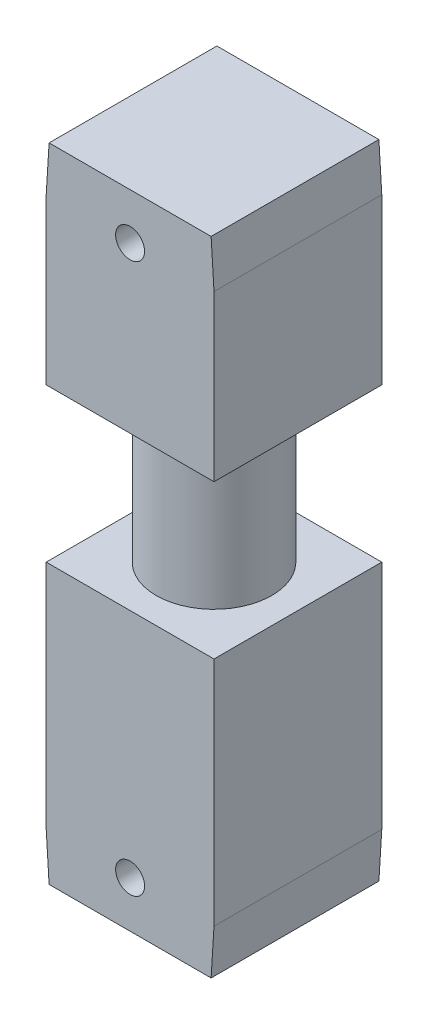
SolidWorks part; units mm, degrees
ref_plane "Front Plane" through (0, 0, 0) normal (0, 0, 1) x (1, 0, 0)
ref_plane "Top Plane" through (0, 0, 0) normal (0, 1, 0) x (1, 0, 0)
ref_plane "Right Plane" through (0, 0, 0) normal (1, 0, 0) x (0, 0, -1)
sketch "Sketch1" plane through (0, 0, 0) normal (0, 0, 1) x (1, 0, 0)
  line L0 (0, 0) -> (0, 106.5273) construction
  line L12 (-14.5, 40) -> (14.5, 40)
  line L13 (-14.5, 66.5273) -> (14.5, 66.5273)
  line L14 (-30, 0) -> (30, 0) construction
  line L16 (-30, 95) -> (30, 95) construction
  line L17 (-30, 103) -> (14, 103) construction
  line L18 (-30, -8) -> (14, -8) construction
  line L19 (-30, 53.2637) -> (30, 53.2637) construction
  line L20 (-14.5, 40) -> (-14.5, 0)
  line L21 (14.5, 40) -> (14.5, 0)
  line L22 (-14, 103) -> (14, 103)
  line L23 (-14.5, 66.5273) -> (-14.5, 95)
  line L24 (-14.5, 95) -> (-14, 103)
  line L25 (14.5, 66.5273) -> (14.5, 95)
  line L26 (14.5, 95) -> (14, 103)
  line L27 (-14, -8) -> (14, -8)
  line L28 (-14.5, 0) -> (-14, -8)
  line L29 (14, -8) -> (14.5, 0)
  circle A12 centre (0, 95) radius 2.5
  circle A13 centre (0, 0) radius 2.5
  point P20 (0, 53.2637)
  point P21 (-8, 103)
  point P34 (-8, -8)
  point P37 (0, 0)
  point P48 (14, -8)
  point P51 (14, 103)
  dimension "D7" = 95
  dimension "D8" = 8
  dimension "D1" = 14.5
  dimension "D9" = 8
extrude "Boss-Extrude1" add sketch "Sketch1" along normal blind 29
sketch "Sketch3" plane through (0, 40, 0) normal (0, 1, 0) x (1, 0, 0)
  line L0 (0, -1) -> (0, -28) construction
  circle A0 centre (0, -14.5) radius 10
  point P4 (0, 0)
  point P8 (0, 0)
  point P9 (0, 0)
  point P10 (0, 0)
extrude "Boss-Extrude2" add sketch "Sketch3" along normal up to surface (26.5273 mm away) up to face at (0, 66.5273, 14.5)
